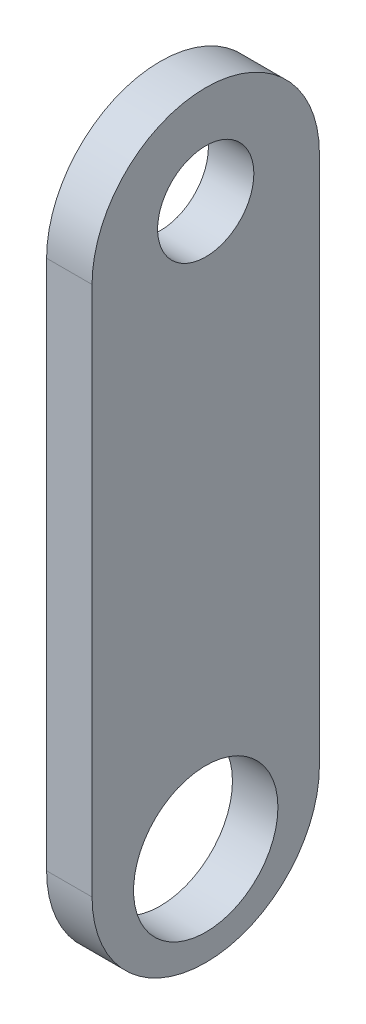
SolidWorks part; units mm, degrees
material "Acrylic (Medium-high impact)"
ref_plane "Alzado" through (0, 0, 0) normal (0, 0, 1) x (1, 0, 0)
ref_plane "Planta" through (0, 0, 0) normal (0, 1, 0) x (1, 0, 0)
ref_plane "Vista lateral" through (0, 0, 0) normal (1, 0, 0) x (0, 0, -1)
sketch "Sketch3" plane through (0, 0, 0) normal (1, 0, 0) x (0, 0, -1)
  line L1 (-7.5, -25) -> (7.5, -25)
  line L2 (-7.5, -25) -> (-7.5, 25)
  line L3 (-7.5, 25) -> (7.5, 25)
  line L4 (7.5, -25) -> (7.5, 25)
  line L5 (-7.5, -25) -> (7.5, 25) construction
  line L6 (-7.5, 25) -> (7.5, -25) construction
  point P0 (0, 0)
  dimension "D1" = 50
  dimension "D2" = 15
extrude "Boss-Extrude1" add sketch "Sketch3" along normal blind 3 contours L3 L4 L1 L2
sketch "Sketch4" plane through (3, 0, 0) normal (1, 0, 0) x (0, 0, -1)
  line L0 (0, 0) -> (0, -25) construction
  line L1 (-7.5, -25) -> (7.5, -25) construction
  line L2 (0, 0) -> (0, 25) construction
  line L3 (-7.5, 25) -> (7.5, 25) construction
  line L4 (0, 0) -> (0, 18.5) construction
  line L5 (0, 0) -> (0, -18.5) construction
  circle A0 centre (0, 18.5) radius 3.175
  circle A1 centre (0, -18.5) radius 4.7625
  dimension "D3" = 9.525
  dimension "D1" = 18.5
  dimension "D2" = 18.5
extrude "Cut-Extrude1" cut sketch "Sketch4" against normal blind 5
fillet "Fillet1" 2 edges at (1.5, 25, 7.5) (1.5, 25, -7.5) type full round first side face at (1.5, 0, 7.5) second side face at (1.5, 0, -7.5) middle face at (1.5, 25, 0)
fillet "Fillet2" 2 edges at (1.5, -25, -7.5) (1.5, -25, 7.5) type full round first side face at (1.5, -3.75, -7.5) second side face at (1.5, -3.75, 7.5) middle face at (1.5, -25, 0)
